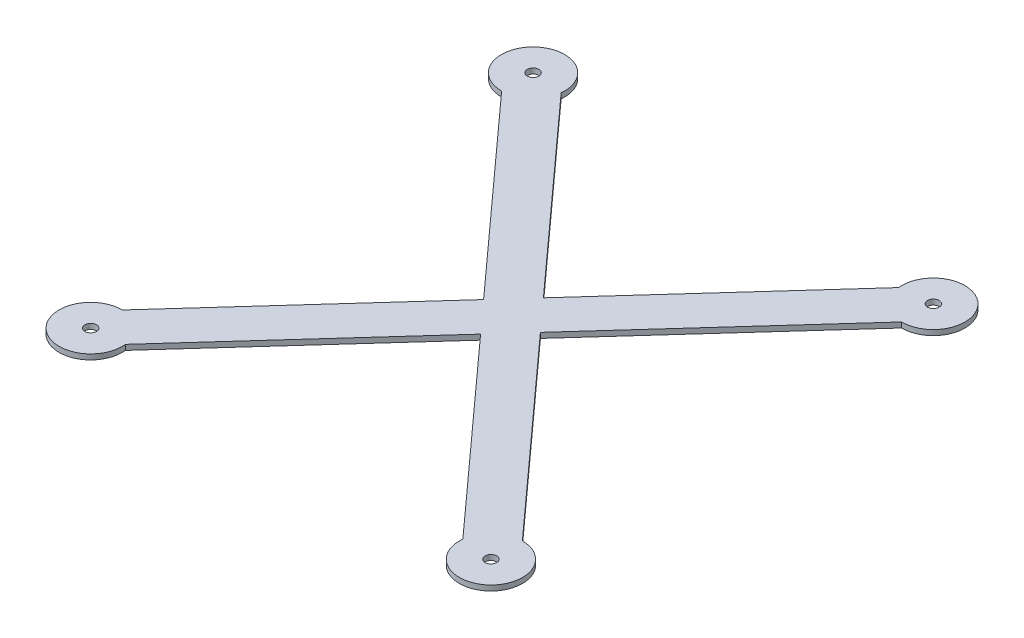
SolidWorks part; units mm, degrees
ref_plane "Front Plane" through (0, 0, 0) normal (0, 0, 1) x (1, 0, 0)
ref_plane "Top Plane" through (0, 0, 0) normal (0, 1, 0) x (1, 0, 0)
ref_plane "Right Plane" through (0, 0, 0) normal (1, 0, 0) x (0, 0, -1)
sketch "Sketch1" plane through (0, 0, 0) normal (0, 1, 0) x (1, 0, 0)
  line L0 (0, 18.9294) -> (101.7062, 131.3415)
  line L1 (-120.65, -133.35) -> (120.65, -133.35) construction
  line L2 (-120.65, -133.35) -> (-120.65, 133.35) construction
  line L3 (-120.65, 133.35) -> (120.65, 133.35) construction
  line L4 (120.65, -133.35) -> (120.65, 133.35) construction
  line L5 (-120.65, -133.35) -> (120.65, 133.35) construction
  line L6 (-120.65, 133.35) -> (120.65, -133.35) construction
  line L7 (0, 18.9294) -> (-101.7062, 131.3415)
  line L8 (17.1266, 0) -> (120.5412, -114.3003)
  line L9 (17.1266, 0) -> (120.5412, 114.3003)
  line L10 (0, -18.9294) -> (101.7062, -131.3415)
  line L11 (0, -18.9294) -> (-101.7062, -131.3415)
  line L12 (-120.5412, -114.3003) -> (-17.1266, 0)
  line L13 (-17.1266, 0) -> (-120.5412, 114.3003)
  line L14 (-17.1266, 0) -> (0, 18.9294) construction
  line L15 (0, 18.9294) -> (17.1266, 0) construction
  circle A0 centre (120.65, 133.35) radius 3.5
  circle A1 centre (-120.65, 133.35) radius 3.5
  circle A2 centre (-120.65, -133.35) radius 3.5
  circle A3 centre (120.65, -133.35) radius 3.5
  circle A4 centre (120.65, 133.35) radius 19.05
  circle A5 centre (-120.65, 133.35) radius 19.05
  circle A6 centre (-120.65, -133.35) radius 19.05
  circle A7 centre (120.65, -133.35) radius 19.05
  point P0 (0, 0)
  point P21 (8.5633, 9.4647)
  point P23 (-8.5633, 9.4647)
  dimension "D3" = 7
  dimension "D6" = 38.1
  dimension "D1" = 241.3
  dimension "D2" = 266.7
  dimension "D5" = 25.4
extrude "Boss-Extrude1" add sketch "Sketch1" along normal blind 3.175 contours A6 A2 | A7 L8 L9 A4 L0 L7 A5 L13 L12 A6 L11 L10 | A7 A3 | A4 A0 | A5 A1 region at (0, 0, 0) region at (119.6728, 0, -151.8354) region at (-108.2306, 0, -119.6233) region at (133.7019, 0, 120.2233) region at (-108.2306, 0, 119.6233)
